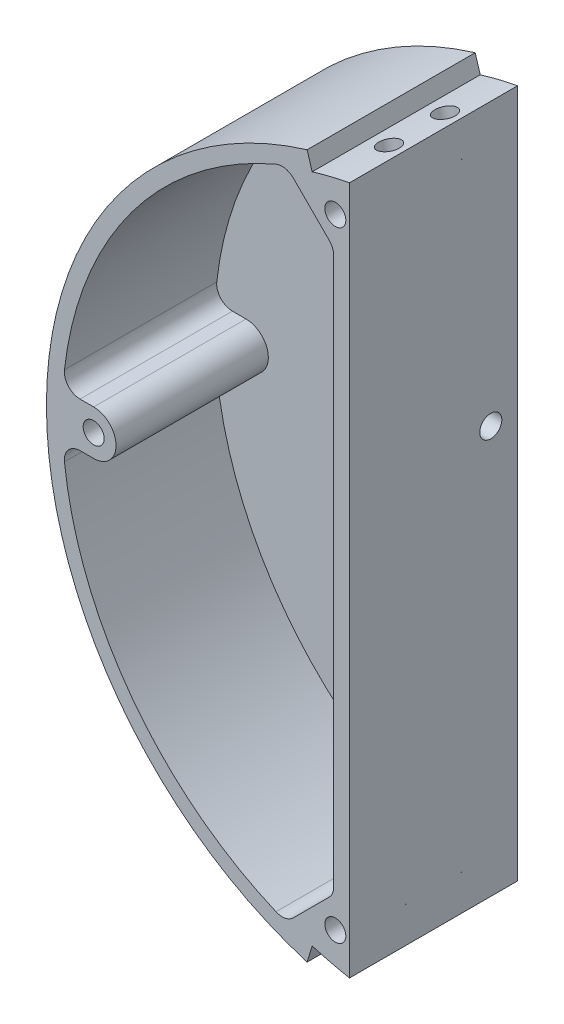
SolidWorks part; units mm, degrees
ref_plane "Front Plane" through (0, 0, 0) normal (0, 0, 1) x (1, 0, 0)
ref_plane "Top Plane" through (0, 0, 0) normal (0, 1, 0) x (1, 0, 0)
ref_plane "Right Plane" through (0, 0, 0) normal (1, 0, 0) x (0, 0, -1)
sketch "Sketch1" plane through (0, 0, 0) normal (0, 0, 1) x (1, 0, 0)
  line L0 (-12.3, -68.9109) -> (-12.3, 68.9109)
  line L1 (-15, 59) -> (-15, -59) construction
  line L5 (-61, 0) -> (0, 0) construction
  circle A2 centre (-15, 59) radius 1.25
  circle A4 centre (-61, 0) radius 1.25
  circle A5 centre (-15, -59) radius 1.25
  arc A6 (-12.3, 68.9109) -> (-12.3, -68.9109) centre (0, 0) ccw
  circle A7 centre (0, 0) radius 65.5 construction
  circle A8 centre (-15, 59) radius 3 construction
  circle A9 centre (-61, 0) radius 3 construction
  circle A10 centre (-15, -59) radius 3 construction
  point P6 (-15, 0)
  dimension "D2" = 2.5
  dimension "D6" = 118
  dimension "D7" = 131
  dimension "D8" = 2.5
  dimension "D4" = 70
  dimension "D3" = 2.5
  dimension "D10" = 6
  dimension "D1" = 12.3
  dimension "D5" = 15
  dimension "D9" = 61
extrude "Boss-Extrude2" add sketch "Sketch1" along normal blind 32
shell "Shell1" thickness 3 removed face at (-13.75, 59, 32)
sketch "Sketch10" plane through (0, 0, 3) normal (0, 0, 1) x (1, 0, 0)
  line L0 (-15.3, 53.2896) -> (-24.4068, 62.3964)
  line L1 (-15.3, -54.7606) -> (-15.3, 54.7606) construction
  line L2 (-15.3, -53.2896) -> (-24.4068, -62.3964)
  line L3 (-15.3, -54.7606) -> (-15.3, 54.7606) construction
  line L4 (-15.3, 65.2297) -> (-15.3, 60.2135)
  line L5 (-15.3, 57.7865) -> (-15.3, 53.2896)
  line L6 (-15.3, 63.2394) -> (-15.3, 65.2297) construction
  line L7 (-15.3, -65.2297) -> (-15.3, -60.2135)
  line L8 (-15.3, -57.7865) -> (-15.3, -53.2896)
  line L9 (-61, -4.25) -> (-63.588, -4.25)
  line L10 (-61, 4.25) -> (-63.588, 4.25)
  arc A0 (-24.4068, 62.3964) -> (-15.3, 65.2297) centre (0, 0) cw
  arc A1 (-63.588, -4.25) -> (-66.5687, -7.5898) centre (-63.588, -7.25) ccw
  arc A2 (-15.3, 65.2297) -> (-15.3, -65.2297) centre (0, 0) ccw construction
  arc A3 (-15.3, 65.2297) -> (-15.3, -65.2297) centre (0, 0) ccw construction
  arc A4 (-15.3, -54.7606) -> (-15.3, -63.2394) centre (-15, -59) ccw construction
  arc A5 (-15.3, 63.2394) -> (-15.3, 54.7606) centre (-15, 59) ccw construction
  arc A6 (-15.3, -65.2297) -> (-24.4068, -62.3964) centre (0, 0) cw
  circle A7 centre (-15, 59) radius 1.25 construction
  arc A8 (-15.3, 60.2135) -> (-15.3, 57.7865) centre (-15, 59) ccw
  circle A9 centre (-15, -59) radius 1.25 construction
  arc A10 (-15.3, -60.2135) -> (-15.2655, -57.7785) centre (-15, -59) cw
  arc A11 (-61, 4.25) -> (-61, -4.25) centre (-61, 0) cw
  circle A12 centre (-61, 0) radius 4.25 construction
  circle A13 centre (-61, 0) radius 4.25 construction
  arc A14 (-63.588, 4.25) -> (-66.5687, 7.5898) centre (-63.588, 7.25) cw
  arc A15 (-66.5687, 7.5898) -> (-66.5687, -7.5898) centre (0, 0) ccw
  circle A16 centre (-61, 0) radius 1.25
  point P57 (-66.8651, 4.25)
  line M8 (-15.3, 63.2394) -> (-15.3, 65.2297)
  arc M9 (-15.3, 65.2297) -> (-15.3, -65.2297) centre (0, 0) ccw
  line M10 (-15.3, -65.2297) -> (-15.3, -63.2394)
  arc M11 (-15.3, -63.2394) -> (-15.3, -54.7606) centre (-15, -59) cw
  line M12 (-15.3, -54.7606) -> (-15.3, 54.7606)
  arc M13 (-15.3, 54.7606) -> (-15.3, 63.2394) centre (-15, 59) cw
  circle M14 centre (-61, 0) radius 4.25
  dimension "D3" = 3
  dimension "D1" = 135
  dimension "D2" = 135
extrude "Boss-Extrude6" add sketch "Sketch10" along normal up to surface (29 mm away) contours L10 A14 A1 L9 M9 M14 | A16 M14 | L7 A10 L8 M11 | L2 M11 M9 M10 | L0 M13 M8 M9 | A8 L4 L5 M13 | L2 M12 M11 | L0 M12 M13 region at (-16.0191, 54.4613, 3) region at (-17.0571, 59, 3) region at (-19.7689, 61.9404, 3) region at (-16.0191, -54.4613, 3) region at (-19.7689, -61.9404, 3) region at (-17.0571, -59, 3) region at (-65.581, 0, 3) region at (-58.0798, 2.9202, 3) up to face at (-25.2333, 0, 32)
fillet "Fillet1" radius 3 4 edges at (-24.4068, -62.3964, 17.5) (-15.3, -53.2896, 17.5) (-15.3, 53.2896, 17.5) (-24.4068, 62.3964, 17.5)
sketch "Sketch11" plane through (-12.3, 0, 0) normal (1, 0, 0) x (0, 0, -1)
  line L0 (-3, -52.047) -> (-3, 52.047) construction
  circle A0 centre (-5.1, 12) radius 2.1
  dimension "D1" = 4.2
  dimension "D2" = 12
extrude "Cut-Extrude4" cut sketch "Sketch11" against normal blind 10
sketch "Sketch12" plane through (0, 0, 32) normal (0, 0, 1) x (1, 0, 0)
  circle A0 centre (-15, -59) radius 2
  circle A1 centre (-61, 0) radius 2
  circle A2 centre (-15, 59) radius 2
  dimension "D1" = 4
extrude "Thread insert holes" cut sketch "Sketch12" against normal blind 4.78
sketch "Sketch13" plane through (0, 0, 0) normal (0, 0, -1) x (-1, 0, 0)
  circle A0 centre (15, 59) radius 2
  circle A1 centre (61, 0) radius 2
  circle A2 centre (15, -59) radius 2
  dimension "D1" = 4
extrude "Cut-Extrude6" cut sketch "Sketch13" against normal blind 4.78
sketch "Sketch14" plane through (0, 0, 0) normal (0, 0, 1) x (1, 0, 0)
  line L0 (-12.3, -68.9109) -> (-12.3, 68.9109) construction
  line L1 (-20.3654, -66.972) -> (0, 0) construction
  line L2 (0, 0) -> (-20.3654, 66.972) construction
  line L3 (-19.4053, -63.8148) -> (-20.3654, -66.972)
  line L4 (-19.4053, 63.8148) -> (-20.3654, 66.972)
  line L5 (-12.3, 65.5561) -> (-12.3, 68.9109)
  line L6 (-12.3, -65.5561) -> (-12.3, -68.9109)
  arc A0 (-12.3, 68.9109) -> (-20.3654, 66.972) centre (0, 0) ccw
  arc A1 (-12.3, -68.9109) -> (-20.3654, -66.972) centre (0, 0) cw
  arc A2 (-12.3, -65.5561) -> (-19.4053, -63.8148) centre (0, 0) cw
  arc A3 (-12.3, 65.5561) -> (-19.4053, 63.8148) centre (0, 0) ccw
  dimension "D3" = 3.3
  dimension "D4" = 3.3
  dimension "D1" = 8.3
  dimension "D2" = 8.3
extrude "Cut-Extrude7" cut sketch "Sketch14" along normal blind 32
sketch "Sketch15" plane through (0, 0, 0) normal (0, 0, 1) x (1, 0, 0)
  line L0 (-12.3, -65.5561) -> (-12.3, 65.5561) construction
  arc A0 (-12.3, -68.9109) -> (-20.0782, -67.0587) centre (0, 0) cw
  arc A1 (-12.3, 68.9109) -> (-20.0782, 67.0587) centre (0, 0) ccw
  circle A2 centre (0, 0) radius 70 construction
  point P11 (-16.2155, 68.0959)
  point P13 (-16.2155, -68.0959)
  dimension "D2" = 140
  dimension "D1" = 8
  dimension "D3" = 8
sketch3d "3DSketch1"
  line L0 (-16.2155, -68.0959, 0) -> (-16.2155, -68.0959, 32)
  line L2 (-16.2155, 68.0959, 0) -> (-16.2155, 68.0959, 32)
  arc A0 (-12.3, 68.9109, 0) -> (-20.0782, 67.0587, 0) centre (0, 0, 0) ccw construction
  point P3 (69.2739, -10.0559, 42.2332)
  point P9 (0, 0, 70)
  point P10 (0, 0, 0)
  point P12 (0, 0, 0)
ref_plane "Plane1" through (-16.2155, 68.0959, 0) normal (-0.2317, 0.9728, 0) x (0.9728, 0.2317, 0)
ref_plane "Plane2" through (-16.2155, -68.0959, 0) normal (-0.2317, -0.9728, 0) x (-0.9728, 0.2317, 0)
sketch "Sketch16" plane through (-16.2155, 68.0959, 0) normal (-0.2317, 0.9728, 0) x (0.9728, 0.2317, 0)
  line L0 (0, 0) -> (0, -32) construction
  circle A0 centre (0, -10.6667) radius 1.65
  circle A1 centre (0, -21.3333) radius 1.65
  dimension "D1" = 10.6667
  dimension "D3" = 3.3
  dimension "D2" = 21.3333
extrude "Cut-Extrude8" cut sketch "Sketch16" against normal blind 10
sketch "Sketch17" plane through (-16.2155, -68.0959, 0) normal (-0.2317, -0.9728, 0) x (-0.9728, 0.2317, 0)
  line L0 (0, 0) -> (0, -32) construction
  circle A0 centre (0, -10.6667) radius 1.65
  circle A1 centre (0, -21.3333) radius 1.65
  dimension "D1" = 10.6667
  dimension "D2" = 21.3333
  dimension "D3" = 3.3
extrude "Cut-Extrude9" cut sketch "Sketch17" against normal blind 10
sketch "Sketch18" plane through (-16.2155, 68.0959, 0) normal (-0.2317, 0.9728, 0) x (0.9728, 0.2317, 0)
  circle A0 centre (0, -10.6667) radius 2
  circle A1 centre (0, -21.3333) radius 2
  dimension "D1" = 4
  dimension "D2" = 4
extrude "Cut-Extrude10" cut sketch "Sketch18" against normal blind 8
sketch "Sketch19" plane through (-16.2155, -68.0959, 0) normal (-0.2317, -0.9728, 0) x (-0.9728, 0.2317, 0)
  circle A0 centre (0, -10.6667) radius 2
  circle A1 centre (0, -21.3333) radius 2
  dimension "D1" = 4
extrude "Cut-Extrude11" cut sketch "Sketch19" against normal blind 8
